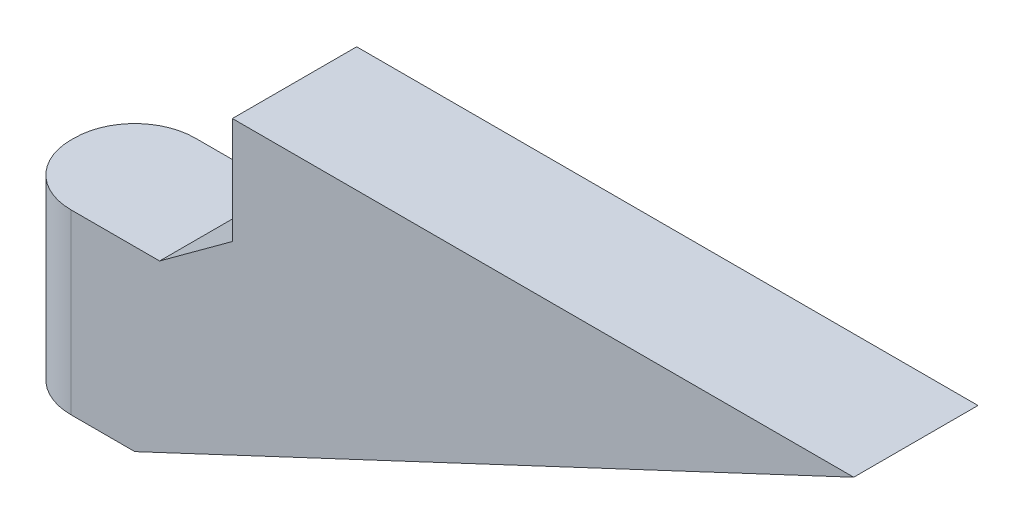
SolidWorks part; units mm, degrees
ref_plane "Front Plane" through (0, 0, 0) normal (0, 0, 1) x (1, 0, 0)
ref_plane "Top Plane" through (0, 0, 0) normal (0, 1, 0) x (1, 0, 0)
ref_plane "Right Plane" through (0, 0, 0) normal (1, 0, 0) x (0, 0, -1)
sketch "Sketch1" plane through (0, 0, 0) normal (0, 0, 1) x (1, 0, 0)
  line L0 (-30.1625, 0.635) -> (-19.4945, 0.635)
  line L1 (30.1625, 12.065) -> (-30.1625, 12.065)
  line L2 (30.1625, 12.065) -> (30.1625, -12.065)
  line L3 (30.1625, -12.065) -> (-30.1625, -12.065)
  line L4 (-30.1625, 12.065) -> (-30.1625, -12.065)
  line L5 (30.1625, 12.065) -> (-30.1625, -12.065) construction
  line L6 (30.1625, -12.065) -> (-30.1625, 12.065) construction
  line L7 (-14.2875, 12.065) -> (-14.2875, 4.445)
  line L8 (-14.2875, 4.445) -> (-19.4945, 0.635)
  line L9 (-14.2875, 4.445) -> (-14.2875, -12.065) construction
  line L10 (-21.2725, -12.065) -> (30.1625, 12.065)
  point P0 (0, 0)
  point P6 (-30.1625, 0.635)
  point P9 (-14.2875, 12.065)
  point P12 (-21.2725, -12.065)
  dimension "D1" = 24.13
  dimension "D2" = 60.325
  dimension "D3" = 12.7
  dimension "D4" = 10.668
  dimension "D5" = 15.875
  dimension "D6" = 8.89
  dimension "D7" = 7.62
extrude "Boss-Extrude1" add sketch "Sketch1" along normal blind 8.89 contours L3 L10 L1 L7 L8 L0 L4 region at (-6.3362, 2.0532, 0)
fillet "Fillet1" radius 4.318 2 edges at (-30.1625, -5.715, 0) (-30.1625, -5.715, 8.89)
